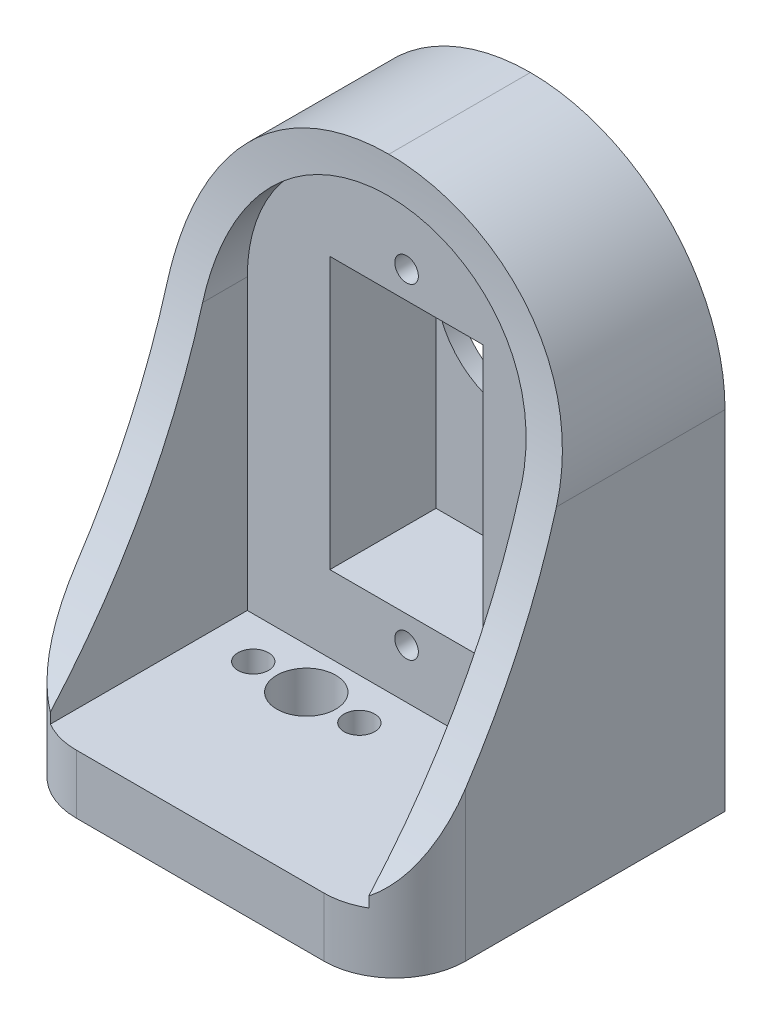
SolidWorks part; units mm, degrees
ref_plane "前视基准面" through (0, 0, 0) normal (0, 0, 1) x (1, 0, 0)
ref_plane "上视基准面" through (0, 0, 0) normal (0, 1, 0) x (1, 0, 0)
ref_plane "右视基准面" through (0, 0, 0) normal (1, 0, 0) x (0, 0, -1)
sketch "草图2" plane through (0, 0, 0) normal (0, 1, 0) x (1, 0, 0)
  line L1 (-16.5, 14) -> (16.5, 14)
  line L2 (-16.5, 14) -> (-16.5, -14)
  line L3 (-16.5, -14) -> (16.5, -14)
  line L4 (16.5, 14) -> (16.5, -14)
  line L5 (0, -14) -> (0, 14) construction
  line L6 (-16.5, 0) -> (16.5, 0) construction
  point P0 (0, 0)
  dimension "D1" = 33
  dimension "D2" = 28
extrude "凸台-拉伸1" add sketch "草图2" along normal blind 46
sketch "草图3" plane through (16.5, 0, 0) normal (1, 0, 0) x (0, 0, -1)
  line L0 (14, 46) -> (14, 0) construction
  line L1 (-14, 46) -> (3.5, 46)
  line L2 (-14, 46) -> (-14, 5)
  line L3 (-14, 5) -> (3.5, 5)
  line L4 (3.5, 46) -> (3.5, 5)
  line L5 (-14, 0) -> (14, 0) construction
  dimension "D1" = 10.5
  dimension "D2" = 5
extrude "切除-拉伸1" cut sketch "草图3" against normal through all
sketch "草图4" plane through (16.5, 0, 0) normal (1, 0, 0) x (0, 0, -1)
  line L0 (3.5, 46) -> (2, 46)
  line L1 (-14, 5) -> (3.5, 5)
  line L2 (3.5, 5) -> (3.5, 46)
  arc A0 (2, 46) -> (-14, 5) centre (-58.5312, 46) cw
  dimension "D1" = 1.5
extrude "凸台-拉伸2" add sketch "草图4" against normal blind 3
mirror "镜向1" about plane through (0, 0, 0) normal (1, 0, 0) of "凸台-拉伸2"
sketch "草图5" plane through (13.5, 0, 0) normal (-1, 0, 0) x (0, 0, 1)
  line L0 (-3.5, 43) -> (-1.9256, 43)
  line L3 (-3.5, 46) -> (-3.5, 5)
  line L4 (-3.5, 5) -> (14, 5)
  line L5 (-2, 46) -> (-3.5, 46)
  line L6 (-3.5, 46) -> (-3.5, 5)
  line L7 (-3.5, 5) -> (14, 5)
  line L8 (-2, 46) -> (-3.5, 46)
  arc A1 (-2, 46) -> (14, 5) centre (58.5312, 46) ccw
  arc A2 (-2, 46) -> (14, 5) centre (58.5312, 46) ccw
  line M6 (-3.5, 46) -> (-3.5, 5)
  arc M8 (14, 5) -> (-2, 46) centre (58.5312, 46) cw
  line M9 (-2, 46) -> (-3.5, 46)
  dimension "D2" = 3
  dimension "D1" = 0
extrude "凸台-拉伸3" add sketch "草图5" along normal up to surface (27 mm away) contours L0 M6 M8 M9 region at (13.5, 44.4878, -2.7374) up to face at (-13.5, 25.1236, 0.2854)
fillet "圆角1" radius 13.5 2 edges at (-13.5, 43, -2.7128) (13.5, 43, -2.7128)
fillet "圆角2" radius 16.5 2 edges at (-16.5, 46, -8) (16.5, 46, -8)
fillet "圆角3" radius 6 2 edges at (16.5, 2.5, 14) (-16.5, 2.5, 14)
sketch "草图6" plane through (0, 0, -3.5) normal (0, 0, 1) x (1, 0, 0)
  line L0 (0, -15.4) -> (0, 15.4) construction
  line L1 (-6.5, 34.5) -> (6.5, 34.5)
  line L2 (-6.5, 34.5) -> (-6.5, 11.5)
  line L3 (-6.5, 11.5) -> (6.5, 11.5)
  line L4 (6.5, 34.5) -> (6.5, 11.5)
  line L5 (0, 11.5) -> (0, 34.5) construction
  line L6 (-6.5, 23) -> (6.5, 23) construction
  line L7 (-13.5, 5) -> (13.5, 5) construction
  point P0 (0, 23)
  dimension "D1" = 13
  dimension "D2" = 23
  dimension "D3" = 6.5
extrude "切除-拉伸2" cut sketch "草图6" against normal blind 9
sketch "草图7" plane through (0, 0, -12.5) normal (0, 0, 1) x (1, 0, 0)
  line L0 (0, -15.4) -> (0, 15.4) construction
  line L1 (6.5, 34.5) -> (-6.5, 34.5) construction
  circle A0 centre (0, 28) radius 6.5
  dimension "D1" = 13
  dimension "D2" = 6.5
extrude "切除-拉伸3" cut sketch "草图7" against normal through all
sketch "草图8" plane through (0, 0, -3.5) normal (0, 0, 1) x (1, 0, 0)
  line L0 (0, -15.4) -> (0, 15.4) construction
  line L1 (0, 36.8) -> (0, 9.2) construction
  line L2 (6.5, 34.5) -> (-6.5, 34.5) construction
  circle A0 centre (0, 36.8) radius 1
  circle A1 centre (0, 9.2) radius 1
  dimension "D1" = 2
  dimension "D2" = 2
  dimension "D3" = 2.3
  dimension "D4" = 27.6
extrude "切除-拉伸4" cut sketch "草图8" against normal blind 8
sketch "草图9" plane through (0, 5, 0) normal (0, 1, 0) x (1, 0, 0)
  line L0 (-16.5, -0.2922) -> (-16.5, 14) construction
  circle A0 centre (-0.5, 0) radius 1.3
  circle A1 centre (-5, 0) radius 2.5
  circle A2 centre (-9.5, 0) radius 1.3
  dimension "D1" = 2.6
  dimension "D2" = 5
  dimension "D6" = 2.6
  dimension "D3" = 4.5
  dimension "D4" = 9
  dimension "D5" = 11.5
extrude "切除-拉伸5" cut sketch "草图9" against normal through all
